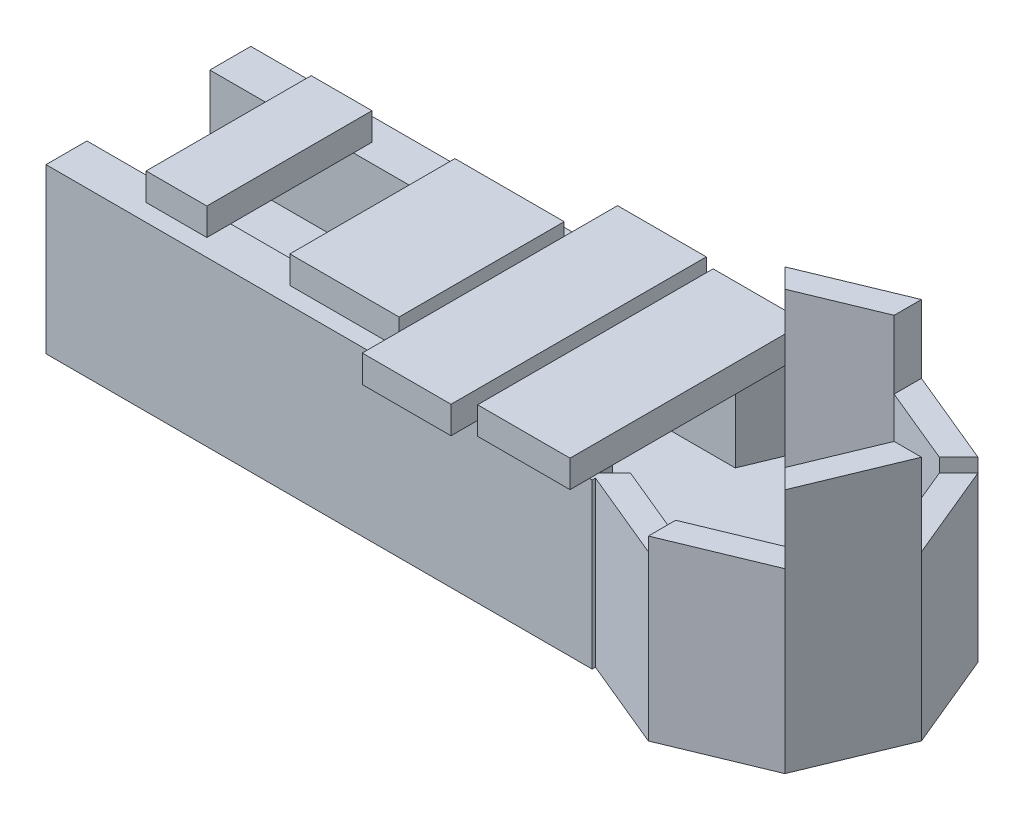
SolidWorks part; units mm, degrees
ref_plane "Alzado" through (0, 0, 0) normal (0, 0, 1) x (1, 0, 0)
ref_plane "Planta" through (0, 0, 0) normal (0, 1, 0) x (1, 0, 0)
ref_plane "Vista lateral" through (0, 0, 0) normal (1, 0, 0) x (0, 0, -1)
sketch "Croquis1" plane through (0, 0, 0) normal (0, 1, 0) x (1, 0, 0)
  line L1 (-10, -3.75) -> (10, -3.75)
  line L2 (-10, -3.75) -> (-10, 3.75)
  line L3 (-10, 3.75) -> (10, 3.75)
  line L4 (10, -3.75) -> (10, 3.75)
  line L5 (-10, -3.75) -> (10, 3.75) construction
  line L6 (-10, 3.75) -> (10, -3.75) construction
  line L7 (-10, 3.75) -> (10, 3.75)
  line L8 (-10, 3.75) -> (-10, 2.25)
  line L9 (-10, 2.25) -> (10, 2.25)
  line L10 (10, 3.75) -> (10, 2.25)
  line L11 (-10, -3.75) -> (10, -3.75)
  line L12 (-10, -3.75) -> (-10, -2.25)
  line L13 (-10, -2.25) -> (10, -2.25)
  line L14 (10, -3.75) -> (10, -2.25)
  line L18 (9.7717, 3.5355) -> (10.4788, 2.8284)
  line L19 (13.3072, 5) -> (9.7717, 3.5355)
  line L20 (9.7717, 3.5355) -> (8.3072, 0)
  line L21 (8.3072, 0) -> (9.7717, -3.5355)
  line L22 (9.7717, -3.5355) -> (13.3072, -5)
  line L23 (13.3072, -5) -> (16.8427, -3.5355)
  line L24 (16.8427, -3.5355) -> (18.3072, 0)
  line L25 (18.3072, 0) -> (16.8427, 3.5355)
  line L26 (16.8427, 3.5355) -> (13.3072, 5)
  line L27 (13.3072, -4) -> (16.1356, -2.8284)
  line L28 (16.1356, -2.8284) -> (17.3072, 0)
  line L29 (17.3072, 0) -> (16.1356, 2.8284)
  line L30 (16.1356, 2.8284) -> (13.3072, 4)
  line L31 (13.3072, 4) -> (10.4788, 2.8284)
  line L32 (10.4788, 2.8284) -> (9.3072, 0)
  line L33 (9.3072, 0) -> (10.4788, -2.8284)
  line L34 (10.4788, -2.8284) -> (13.3072, -4)
  line L35 (13.3072, 5) -> (13.3072, 4)
  line L36 (16.8427, 3.5355) -> (16.1356, 2.8284)
  line L37 (18.3072, 0) -> (17.3072, 0)
  line L38 (16.8427, -3.5355) -> (16.1356, -2.8284)
  line L39 (13.3072, -5) -> (13.3072, -4)
  line L40 (9.7717, -3.5355) -> (10.4788, -2.8284)
  line L41 (8.3072, 0) -> (9.3072, 0)
  circle A0 centre (13.3072, 0) radius 5 construction
  circle A1 centre (13.3072, 0) radius 4 construction
  circle A2 centre (13.3072, 0) radius 4.6194 construction
  circle A3 centre (13.3072, 0) radius 3.6955 construction
  point P0 (0, 0)
  point P13 (16.8427, 3.5355)
  point P14 (13.3072, 5)
  point P15 (9.7717, 3.5355)
  point P16 (8.3072, 0)
  point P17 (9.7717, -3.5355)
  point P18 (13.3072, -5)
  point P19 (16.8427, -3.5355)
  point P20 (18.3072, 0)
  dimension "D3" = 10
  dimension "D4" = 1
  dimension "D1" = 7.5
  dimension "D2" = 20
extrude "Saliente-Extruir1" add sketch "Croquis1" along normal blind 3 contours A0 L13 L2 L1 | A0 L3 L2 L9 region at (-0.2144, 0, 3.0046) region at (-0.2144, 0, -3.0046)
extrude "Saliente-Extruir2" add sketch "Croquis1<3>" along normal blind 6 separate body contours L35 L19 L10 L18 L31 | L38 L24 L37 L28 | L10 L19 L18 region at (17.164, 0, 1.5975) region at (9.9239, 0, -3.4909) region at (11.7306, 0, -3.8611)
sketch "Croquis1<3>" plane through (0, 0, 0) normal (0, 1, 0) x (1, 0, 0) same geometry as "Croquis1"
extrude "Saliente-Extruir3" add sketch "Croquis1<4>" along normal blind 3.5 separate body contours L36 L26 L35 L30 | L39 L23 L38 L27 region at (14.9047, 0, 3.8568) region at (14.9047, 0, -3.8568)
sketch "Croquis1<4>" plane through (0, 0, 0) normal (0, 1, 0) x (1, 0, 0) same geometry as "Croquis1"
extrude "Saliente-Extruir4" add sketch "Croquis1<5>" along normal blind 3 separate body contours L40 L14 L22 L39 L34 | L37 L25 L36 L29 | L40 L22 L14 region at (9.9239, 0, 3.4909) region at (11.7306, 0, 3.8611) region at (17.164, 0, -1.5975)
sketch "Croquis1<5>" plane through (0, 0, 0) normal (0, 1, 0) x (1, 0, 0) same geometry as "Croquis1"
sketch "Croquis2" plane through (0, 0, 0) normal (0, -1, 0) x (1, 0, 0)
  line L1 (-10, 3.75) -> (10, 3.75)
  line L2 (-10, 3.75) -> (-10, -3.75)
  line L3 (-10, -3.75) -> (10, -3.75)
  line L4 (10, 3.75) -> (10, -3.75)
  line L5 (13.3072, 5) -> (9.7717, 3.5355)
  line L6 (9.7717, 3.5355) -> (8.3072, 0)
  line L7 (8.3072, 0) -> (9.7717, -3.5355)
  line L8 (9.7717, -3.5355) -> (13.3072, -5)
  line L9 (13.3072, -5) -> (16.8427, -3.5355)
  line L10 (16.8427, -3.5355) -> (18.3072, 0)
  line L11 (18.3072, 0) -> (16.8427, 3.5355)
  line L12 (16.8427, 3.5355) -> (13.3072, 5)
  circle A0 centre (13.3072, 0) radius 4.6194 construction
  line M1 (9.7717, 3.5355) -> (10, 3.6301)
  line M2 (10, 3.6301) -> (10, 3.75)
  line M3 (10, 3.75) -> (-10, 3.75)
  line M4 (-10, 3.75) -> (-10, 2.25)
  line M5 (-10, 2.25) -> (9.2392, 2.25)
  line M6 (9.2392, 2.25) -> (9.7717, 3.5355)
extrude "Saliente-Extruir5" add sketch "Croquis2" along normal blind 3 contours L8 L7 L6 L2 L3 L4 M5 | L11 L12 L5 L4 L8 L9 L10 | L7 L8 L4 L6 M1 M6 | M6 M1 M2 M3 M4 M5 region at (-0.2144, 0, 3.0046) region at (-0.5091, 0, -0.7748) region at (13.7208, 0, 0) region at (9.4283, 0, 0)
sketch "Croquis3" plane through (0, -3, 0) normal (0, -1, 0) x (1, 0, 0)
  circle A0 centre (4.3333, 0) radius 1.575
  dimension "D1" = 3.15
extrude "Cortar-Extruir1" cut sketch "Croquis3" against normal blind 2.5
sketch "Croquis4" plane through (0, 3, 0) normal (0, 1, 0) x (1, 0, 0)
  line L1 (6.5193, 4.1603) -> (9.9031, 4.1603)
  line L2 (6.5193, 4.1603) -> (6.5193, -4.464)
  line L3 (6.5193, -4.464) -> (9.9031, -4.464)
  line L4 (9.9031, 4.1603) -> (9.9031, -4.464)
  line L5 (2.7653, 4.4136) -> (6.0152, 4.4136)
  line L6 (2.7653, 4.4136) -> (2.7653, -4.9344)
  line L7 (2.7653, -4.9344) -> (6.0152, -4.9344)
  line L8 (6.0152, 4.4136) -> (6.0152, -4.9344)
  line L9 (-1.7032, 2.928) -> (2.2973, 2.928)
  line L10 (-1.7032, 2.928) -> (-1.7032, -3.1177)
  line L11 (-1.7032, -3.1177) -> (2.2973, -3.1177)
  line L12 (2.2973, 2.928) -> (2.2973, -3.1177)
  line L13 (-6.9662, 2.928) -> (-4.7416, 2.928)
  line L14 (-6.9662, 2.928) -> (-6.9662, -3.1177)
  line L15 (-6.9662, -3.1177) -> (-4.7416, -3.1177)
  line L16 (-4.7416, 2.928) -> (-4.7416, -3.1177)
extrude "Saliente-Extruir6" add sketch "Croquis4" along normal blind 1
